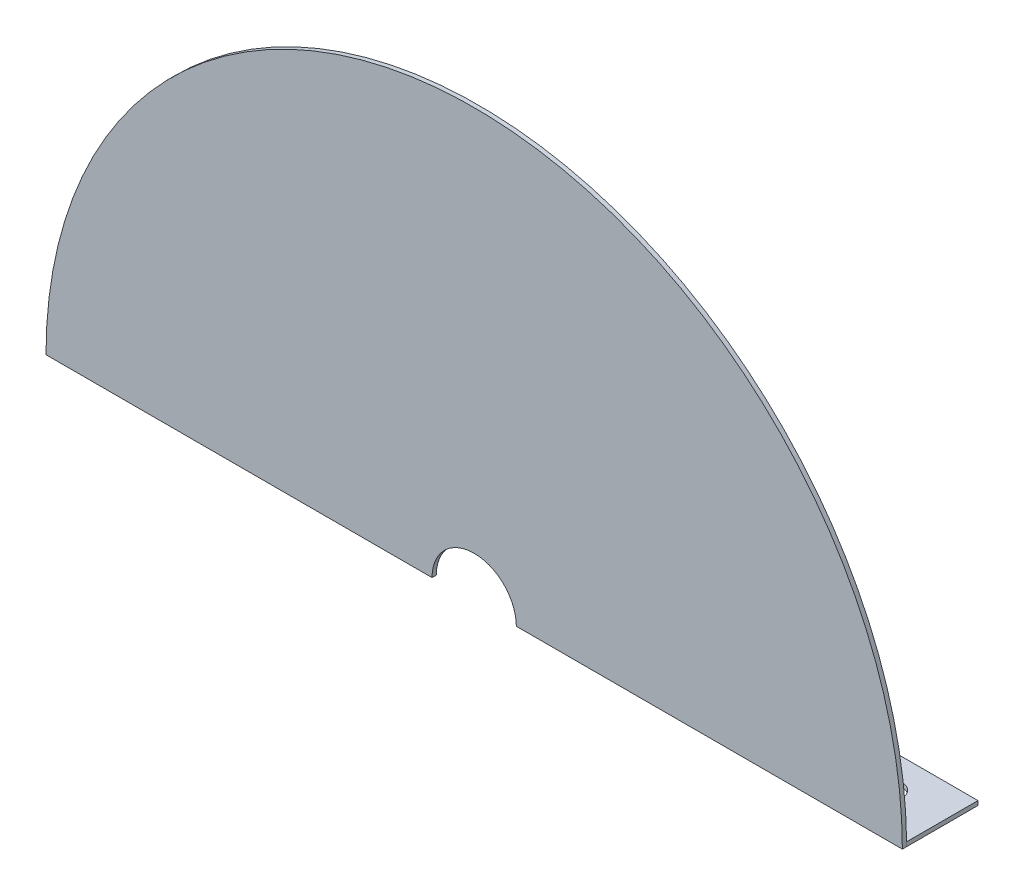
SolidWorks part; units mm, degrees
material "201 Annealed Stainless Steel (SS)"
ref_plane "Front Plane" through (0, 0, 0) normal (0, 0, 1) x (1, 0, 0)
ref_plane "Top Plane" through (0, 0, 0) normal (0, 1, 0) x (1, 0, 0)
ref_plane "Right Plane" through (0, 0, 0) normal (1, 0, 0) x (0, 0, -1)
sketch "Plate shape" plane through (0, 0, 0) normal (0, 0, 1) x (1, 0, 0)
  line L3 (-154.3999, 0) -> (210.7061, 0) construction
  line L4 (0, 152.4) -> (-152.4, 152.4)
  line L5 (0, 152.4) -> (152.4, 152.4)
  line L9 (0, 152.4) -> (0, 0) construction
  line L10 (0, 152.4) -> (30, 152.4) construction
  line L11 (30, 152.4) -> (30, 301.8181) construction
  arc A0 (-152.4, 152.4) -> (152.4, 152.4) centre (0, 152.4) cw
  arc A1 (152.4, 152.4) -> (-152.4, 152.4) centre (0, 152.4) cw construction
  dimension "D1" = 152.4
  dimension "D2" = 30
extrude "Outer casing" add sketch "Plate shape" along normal blind 1.5189
sketch "Sketch1" plane through (0, 0, 1.5189) normal (0, 0, 1) x (1, 0, 0)
  circle A0 centre (0, 152.4) radius 152.4 construction
  arc A1 (152.4, 152.4) -> (-152.4, 152.4) centre (0, 152.4) ccw construction
  circle A2 centre (0, 152.4) radius 15
  dimension "D1" = 30
extrude "Inner Cutout" cut sketch "Sketch1" against normal blind 20
sketch "Sketch3" plane through (0, 0, 1.5189) normal (0, 0, 1) x (1, 0, 0)
  line L0 (30, 152.4) -> (30, 301.8181) construction
  line L1 (15, 152.4) -> (152.4, 152.4) construction
  line L2 (-15, 152.4) -> (15, 152.4) construction
  arc A0 (152.4, 152.4) -> (-152.4, 152.4) centre (0, 152.4) ccw construction
  point P11 (0, 152.4)
  dimension "D1" = 30
sketch "Sketch4" plane through (0, 0, 0) normal (0, 0, -1) x (-1, 0, 0)
  line L0 (-152.4, 152.4) -> (-76.2, 152.4)
  line L1 (-15, 152.4) -> (-152.4, 152.4) construction
  line L2 (-76.2, 152.4) -> (-76.2, 153.9189)
  line L3 (-76.2, 153.9189) -> (-152.4, 153.9189)
  line L4 (-152.4, 153.9189) -> (-152.4, 152.4)
  line L5 (152.4, 152.4) -> (76.2, 152.4)
  line L7 (152.4, 152.4) -> (15, 152.4) construction
  line L8 (76.2, 152.4) -> (76.2, 153.9189)
  line L9 (76.2, 153.9189) -> (152.4, 153.9189)
  line L10 (152.4, 153.9189) -> (152.4, 152.4)
  point P12 (154.6194, 152.4)
  dimension "D1" = 1.5189
  dimension "D2" = 76.2
  dimension "D3" = 1.5189
  dimension "D4" = 76.2
extrude "Boss-Extrude1" add sketch "Sketch4" along normal blind 25.4
sketch "Sketch5" plane through (0, 153.9189, 0) normal (0, 1, 0) x (1, 0, 0)
  line L0 (152.4, 12.7) -> (76.2, 12.7) construction
  line L1 (152.4, 25.4) -> (152.4, 0) construction
  line L2 (76.2, 25.4) -> (76.2, 0) construction
  line L3 (0, -14.8054) -> (0, 14.8054) construction
  circle A0 centre (133.35, 12.7) radius 4.7625
  circle A1 centre (95.25, 12.7) radius 4.7625
  circle A2 centre (-133.35, 12.7) radius 4.7625
  circle A3 centre (-95.25, 12.7) radius 4.7625
  point P10 (136.644, 12.7)
  point P11 (96.1965, 12.7)
  dimension "D3" = 9.525
  dimension "D1" = 38.1
  dimension "D2" = 19.05
extrude "Cut-Extrude1" cut sketch "Sketch5" against normal through all
